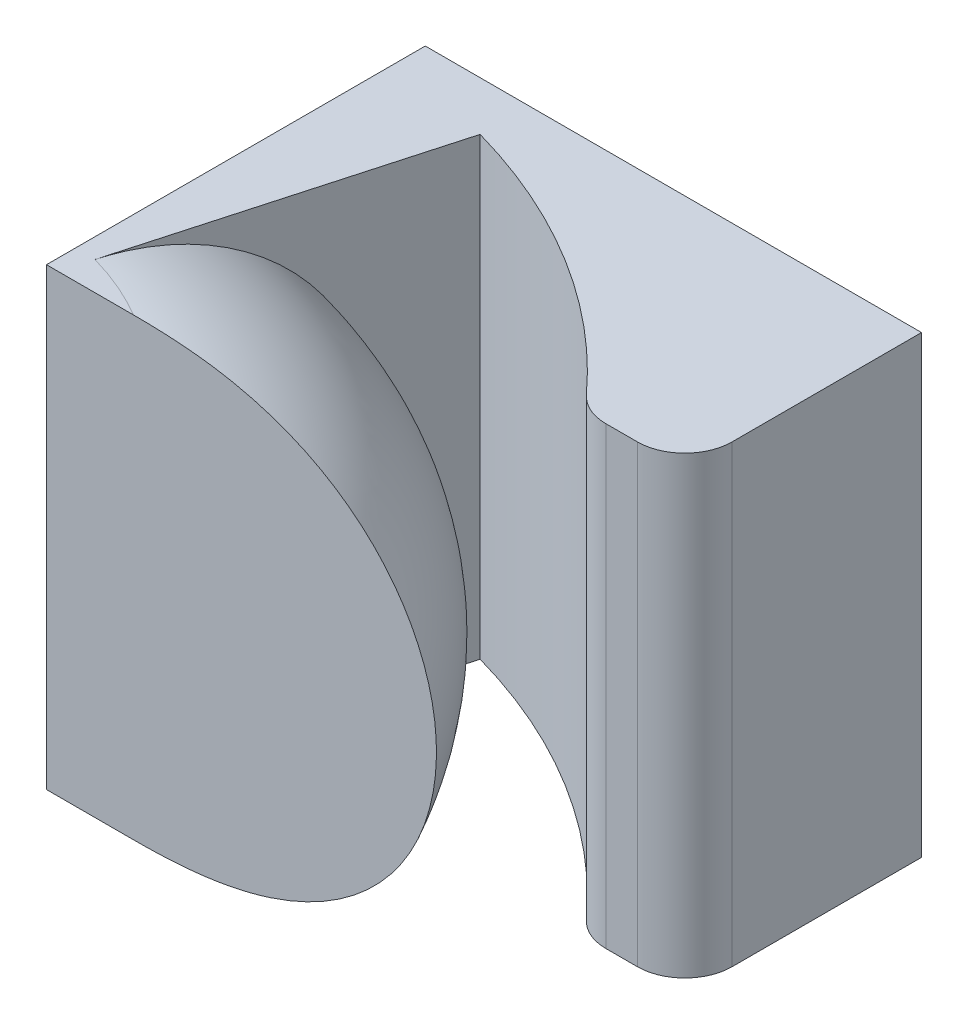
SolidWorks part; units mm, degrees
ref_plane "Plan de face" through (0, 0, 0) normal (0, 0, 1) x (1, 0, 0)
ref_plane "Plan de dessus" through (0, 0, 0) normal (0, 1, 0) x (1, 0, 0)
ref_plane "Plan de droite" through (0, 0, 0) normal (1, 0, 0) x (0, 0, -1)
sketch "Esquisse1" plane through (0, 0, 0) normal (0, 0, 1) x (1, 0, 0)
  line L1 (-26.2021, 24) -> (26.2021, 24)
  line L2 (-26.2021, 24) -> (-26.2021, -24)
  line L3 (-26.2021, -24) -> (26.2021, -24)
  line L4 (26.2021, 24) -> (26.2021, -24)
  line L5 (-26.2021, 24) -> (26.2021, -24) construction
  line L6 (-26.2021, -24) -> (26.2021, 24) construction
  point P0 (0, 0)
  dimension "D1" = 48
extrude "Boss.-Extru.1" add sketch "Esquisse1" along normal blind 40
sketch "Esquisse2" plane through (0, -24, 0) normal (0, -1, 0) x (1, 0, 0)
  line L0 (-15.2259, 5.1859) -> (-17.651, 13.853)
  line L1 (-26.2021, 40) -> (26.2021, 40) construction
  line L2 (15.6114, 25.003) -> (26.2021, 25.003)
  line L3 (26.2021, 40) -> (26.2021, 0) construction
  line L4 (26.2021, 25.003) -> (26.2021, 40)
  line L5 (26.2021, 40) -> (14.9814, 40)
  arc A0 (-17.651, 13.853) -> (14.9814, 40) centre (-32.027, 65.2315) ccw
  arc A1 (-15.2259, 5.1859) -> (15.6114, 25.003) centre (-32.027, 65.2315) ccw
  dimension "D1" = 9
extrude "Enlèv. mat.-Extru.1" cut sketch "Esquisse2" against normal up to next
fillet "Congé1" 2 edges at (1.3335, -24, 23.5963) (1.3335, 24, 23.5963) type full round first side face at (0.2342, -24, 17.9247) second side face at (0.2342, 24, 17.9247) middle face at (-0.0006, 0, 25.2614)
fillet "Congé2" radius 5 2 edges at (26.2021, 0, 25.003) (15.6114, 0, 25.003)
